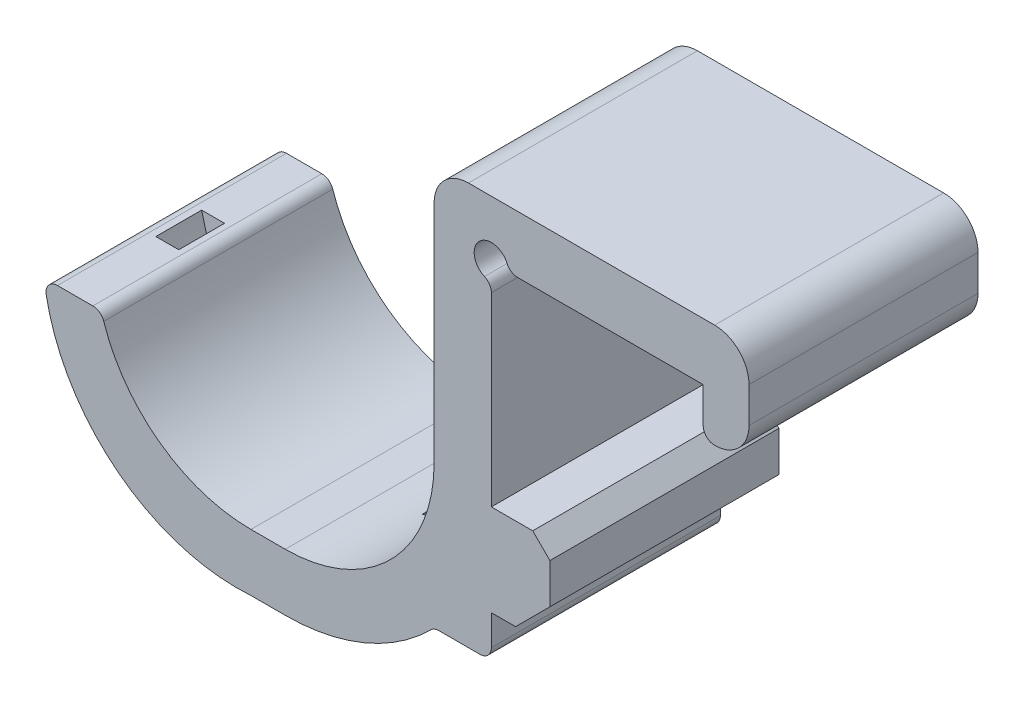
SolidWorks part; units mm, degrees
ref_plane "Front Plane" through (0, 0, 0) normal (0, 0, 1) x (1, 0, 0)
ref_plane "Top Plane" through (0, 0, 0) normal (0, 1, 0) x (1, 0, 0)
ref_plane "Right Plane" through (0, 0, 0) normal (1, 0, 0) x (0, 0, -1)
sketch "Sketch1" plane through (0, 0, 0) normal (0, 0, 1) x (1, 0, 0)
  line L0 (18, 41.408) -> (18, 45.5)
  line L1 (18, 45.5) -> (-0.5, 45.5)
  line L2 (-0.5, 45.5) -> (-0.5, 27)
  line L3 (-0.5, 27) -> (4.6129, 27)
  line L4 (4.6129, 27) -> (4.6129, 19)
  line L5 (4.6129, 19) -> (-0.5, 19)
  line L6 (-0.5, 19) -> (-0.5, 15.3487)
  line L7 (18, 41.408) -> (22, 41.408)
  line L8 (22, 41.408) -> (22, 50.5)
  line L9 (22, 50.5) -> (-5.5, 50.5)
  line L10 (-5.5, 50.5) -> (-5.5, 27.7986)
  line L11 (3, 45) -> (17, 45) construction
  line L12 (17.5, 43.5) -> (17.5, 39) construction
  line L13 (0, 28) -> (0, 42) construction
  line L14 (1.5, 27.5) -> (6, 27.5) construction
  line L16 (-0.5, 15.3487) -> (-5.5, 15.3487)
  line L18 (-18.5, 14.7986) -> (-21.5, 14.7986)
  line L19 (-34.5578, 24.7986) -> (-39.5578, 24.7986)
  line L20 (-21.5, 9.7986) -> (-18.5, 9.7986)
  arc A0 (-5.5, 27.7986) -> (-18.5, 14.7986) centre (-18.5, 27.7986) cw
  arc A1 (-18.5, 9.7986) -> (-5.5, 15.3487) centre (-18.5, 27.7986) ccw
  arc A2 (-21.5, 14.7986) -> (-34.5578, 24.7986) centre (-21.5, 28.3239) cw
  arc A3 (-39.5578, 24.7986) -> (-21.5, 9.7986) centre (-22.6915, 26.7336) ccw
  arc A4 (-0.5, 44) -> (1, 45.5) centre (-0.5, 45.5) cw
  dimension "D8" = 13
  dimension "D14" = 1.5
  dimension "D1" = 5
  dimension "D2" = 4
  dimension "D3" = 0.5
  dimension "D4" = 0.5
  dimension "D5" = 5
  dimension "D6" = 0.5
  dimension "D7" = 0.5
  dimension "D9" = 8
  dimension "D10" = 5
  dimension "D11" = 5
  dimension "D12" = 3
  dimension "D13" = 3
extrude "Boss-Extrude1" add sketch "Sketch1" against normal blind 20 contours L2 A4 L1 L0 L7 L8 L9 L10 A0 L18 A2 L19 A3 L20 A1 L16 L6 L5 L4 L3 region at (18.7382, 43.454, 0)
fillet "Fillet1" radius 3 3 edges at (22, 41.408, -10) (22, 50.5, -10) (-5.5, 50.5, -10)
chamfer "Chamfer1" distance 3 angle 45 1 edges at (4.6129, 19, -10)
fillet "Fillet2" radius 1 7 edges at (18, 41.408, -10) (-0.5, 15.3487, -10) (-5.5, 15.3487, -10) (-34.5578, 24.7986, -10) (-39.5578, 24.7986, -10) (-0.5, 44, -10) (1, 45.5, -10)
ref_plane "Plane1" through (0, 0, -10) normal (0, 0, 1) x (1, 0, 0)
sketch "Sketch3" plane through (0, 0, 0) normal (0, 0, 1) x (1, 0, 0)
  line L0 (-5.5, 47.5) -> (-5.5, 27.7986) construction
  line L1 (-21.5, 13.5935) -> (-18.5, 13.5935)
  line L2 (-21.5, 11.6447) -> (-18.5, 11.6447)
  line L3 (-35.3024, 24.7986) -> (-38.3965, 24.7986) construction
  line L4 (-5.6144, 21.8198) -> (-6.4716, 22.8674)
  line L5 (-4.3466, 26.587) -> (-5.5015, 27.9985)
  line L6 (-14.8635, 14.0668) -> (-14.548, 15.4139)
  line L7 (-10.2471, 16.2368) -> (-9.802, 18.1371)
  line L8 (-5.5, 37.3876) -> (-5.5, 33.5246)
  line L9 (-37.8024, 24.7986) -> (-35.8024, 24.7986)
  arc A0 (-37.8024, 24.7986) -> (-21.5, 11.6447) centre (-21.5, 28.3239) ccw
  arc A1 (-4.3466, 26.587) -> (-5.6144, 21.8198) centre (-18.5, 27.7986) cw
  arc A2 (-10.2471, 16.2368) -> (-14.8635, 14.0668) centre (-18.5, 27.7986) cw
  arc A4 (-35.8024, 24.7986) -> (-21.5, 13.5935) centre (-21.5, 28.3239) ccw
  arc A5 (-35.8976, 25.2105) -> (-21.5, 13.5935) centre (-21.5, 28.3239) ccw construction
  arc A6 (-18.5, 13.5935) -> (-5.5, 33.5246) centre (-18.5, 27.7986) ccw
  arc A8 (-18.5, 11.6447) -> (-5.5, 37.3876) centre (-18.5, 27.7986) ccw
  arc A9 (-5.5015, 27.9985) -> (-6.4716, 22.8674) centre (-18.5, 27.7986) cw
  arc A10 (-9.802, 18.1371) -> (-14.548, 15.4139) centre (-18.5, 27.7986) cw
  arc A11 (-18.5, 14.7986) -> (-5.5, 27.7986) centre (-18.5, 27.7986) ccw construction
  arc A12 (-34.3521, 24.1102) -> (-21.5, 14.7986) centre (-21.5, 28.3239) ccw construction
  point P3 (-36.4728, 24.7986)
  point P10 (0, 0)
  point P17 (-10.333, 17.6843)
  point P18 (0, 0)
  point P20 (0, 0)
  point P21 (0, 0)
  point P29 (-13.1669, 14.2585)
  point P34 (-40.0922, 24.7986)
  point P35 (-4.5, 33.5272)
  point P37 (0, 0)
  point P38 (0, 0)
  point P39 (0, 0)
  point P40 (0, 0)
  point P41 (0, 0)
  point P42 (0, 0)
  point P43 (0, 0)
  point P45 (-5.5, 33.5284)
  point P48 (-7.2439, 21.2948)
  point P49 (-5.969, 24.3382)
  point P50 (-4.9893, 23.0114)
  point P51 (-9.6867, 18.2421)
  point P52 (-14.8475, 14.0232)
  point P54 (-5.5015, 21.7935)
  point P55 (0, 0)
  point P56 (0, 0)
  point P57 (-18.2559, 13.5935)
  line M52 (-35.3024, 24.7986) -> (-38.3965, 24.7986)
  line M75 (-5.5, 47.5) -> (-5.5, 27.7986)
  arc M76 (-5.5, 27.7986) -> (-18.5, 14.7986) centre (-18.5, 27.7986) cw
  dimension "D1" = 2
  dimension "D2" = 4
  dimension "D3" = 0.5
  dimension "D4" = 4
extrude "Cut-Extrude1" cut sketch "Sketch3" against normal blind 2 and the other way blind 2 from surface contours L2 A8 A6 A1 A2 L1 A4 A0 M75 M52 | A1 L5 L4 M75 M76 | A2 L7 L6 M76 region at (-20, 13.1553, 0) region at (-12.2863, 15.8077, 0) region at (-5.3271, 24.7812, 0) starting at plane "Plane1"
chamfer "Chamfer2" distance 1.5 angle 45 1 edges at (4.6129, 27, -10)
